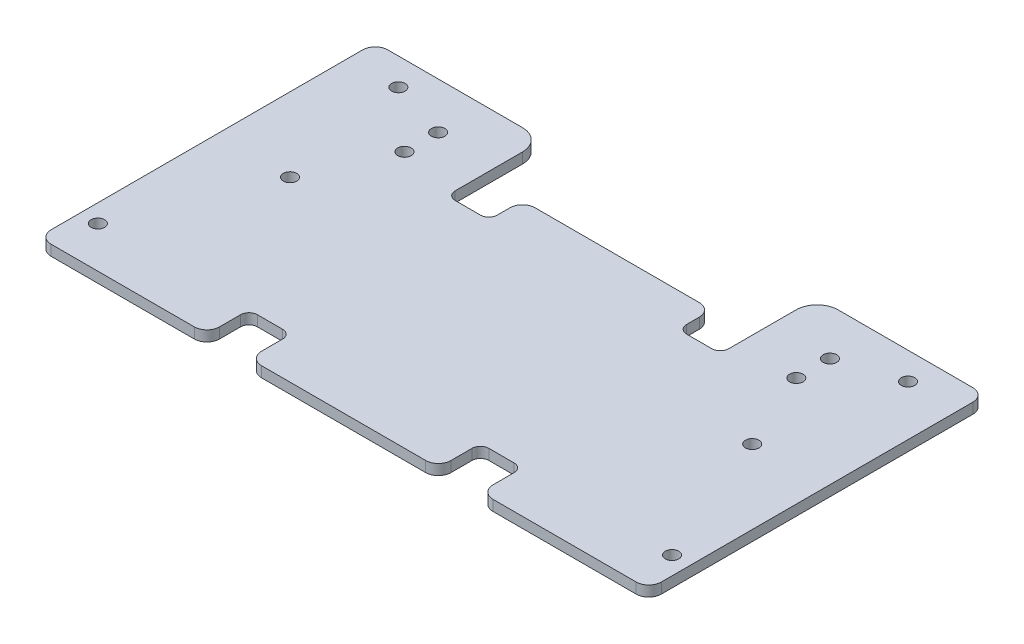
SolidWorks part; units mm, degrees
ref_plane "Front Plane" through (0, 0, 0) normal (0, 0, 1) x (1, 0, 0)
ref_plane "Top Plane" through (0, 0, 0) normal (0, 1, 0) x (1, 0, 0)
ref_plane "Right Plane" through (0, 0, 0) normal (1, 0, 0) x (0, 0, -1)
sketch "Sketch1" plane through (0, 0, 0) normal (0, 1, 0) x (1, 0, 0)
  line L0 (0, 0) -> (0, -101.6)
  line L1 (0, -101.6) -> (184.15, -101.6)
  line L2 (184.15, -101.6) -> (184.15, 0)
  line L4 (50.8, 0) -> (50.8, -19.05)
  line L5 (50.8, -19.05) -> (133.35, -19.05)
  line L6 (133.35, -19.05) -> (133.35, 0)
  line L7 (0, 0) -> (50.8, 0)
  line L8 (133.35, 0) -> (184.15, 0)
  line L9 (50.8, -19.05) -> (50.8, -29.21)
  line L10 (50.8, -29.21) -> (63.5, -29.21)
  line L11 (63.5, -29.21) -> (63.5, -19.05)
  line L12 (133.35, -19.05) -> (133.35, -29.21)
  line L13 (133.35, -29.21) -> (120.65, -29.21)
  line L14 (120.65, -29.21) -> (120.65, -19.05)
  line L15 (50.8, -101.6) -> (50.8, -88.9)
  line L16 (50.8, -88.9) -> (63.5, -88.9)
  line L17 (63.5, -88.9) -> (63.5, -101.6)
  line L18 (120.65, -101.6) -> (120.65, -88.9)
  line L19 (120.65, -88.9) -> (133.35, -88.9)
  line L20 (133.35, -88.9) -> (133.35, -101.6)
  line L21 (92.075, -101.6) -> (92.075, -19.05) construction
  dimension "D1" = 184.15
  dimension "D2" = 82.55
  dimension "D3" = 12.7
  dimension "D4" = 10.16
  dimension "D5" = 19.05
  dimension "D6" = 101.6
  dimension "D7" = 12.7
extrude "Boss-Extrude1" add sketch "Sketch1" along normal blind 3.175 contours L2 L0 L1 | L21 L1 L18 L19 L20 L2 L8 L6 L12 L13 L14 L5 region at (43.2352, 0, 54.2701) region at (140.9148, 0, 54.2701)
fillet "Fillet1" radius 3.81 4 edges at (184.15, 1.5875, 101.6) (0, 1.5875, 101.6) (184.15, 1.5875, 0) (0, 1.5875, 0)
sketch "Sketch2" plane through (0, 3.175, 0) normal (0, 1, 0) x (1, 0, 0)
  line L0 (92.075, -101.6) -> (92.075, -19.05) construction
  line L1 (63.5, -101.6) -> (120.65, -101.6) construction
  line L2 (63.5, -19.05) -> (120.65, -19.05) construction
  circle A4 centre (5.4374, -89.1463) radius 2.032 construction
  circle A5 centre (5.4374, -89.1463) radius 2.032
  circle A6 centre (22.3389, -48.035) radius 2.032 construction
  circle A8 centre (15.1663, -8.1952) radius 2.032 construction
  circle A9 centre (22.3389, -48.035) radius 2.032
  circle A11 centre (15.1663, -8.1952) radius 2.032
  circle A20 centre (178.7126, -89.1463) radius 2.032
  circle A21 centre (161.8111, -48.035) radius 2.032
  circle A24 centre (32.9463, -24.13) radius 2.032 construction
  circle A25 centre (32.9463, -13.97) radius 2.032 construction
  circle A26 centre (32.9463, -24.13) radius 2.032
  circle A27 centre (32.9463, -13.97) radius 2.032
  circle A28 centre (151.2037, -24.13) radius 2.032 construction
  circle A29 centre (151.2037, -13.97) radius 2.032 construction
  circle A30 centre (151.2037, -24.13) radius 2.032
  circle A31 centre (151.2037, -13.97) radius 2.032
  circle A32 centre (151.2037, -24.13) radius 2.032
  circle A33 centre (151.2037, -13.97) radius 2.032
  circle A34 centre (32.9463, -13.97) radius 2.032
  circle A35 centre (32.9463, -24.13) radius 2.032
  circle A36 centre (168.9837, -8.1952) radius 2.032
extrude "Cut-Extrude1" cut sketch "Sketch2" against normal through all contours A11 | A9 | A5 | A26 | A27 | A31 | A30 | A21 | A36 | A20
fillet "Fillet2" radius 6.35 2 edges at (50.8, 1.5875, 0) (133.35, 1.5875, 0)
fillet "Fillet3" radius 2.54 8 edges at (133.35, 1.5875, 29.21) (120.65, 1.5875, 29.21) (50.8, 1.5875, 29.21) (63.5, 1.5875, 29.21) (133.35, 1.5875, 88.9) (120.65, 1.5875, 88.9) (63.5, 1.5875, 88.9) (50.8, 1.5875, 88.9)
fillet "Fillet4" radius 3.81 2 edges at (120.65, 1.5875, 19.05) (63.5, 1.5875, 19.05)
fillet "Fillet5" radius 3.81 4 edges at (133.35, 1.5875, 101.6) (120.65, 1.5875, 101.6) (63.5, 1.5875, 101.6) (50.8, 1.5875, 101.6)
